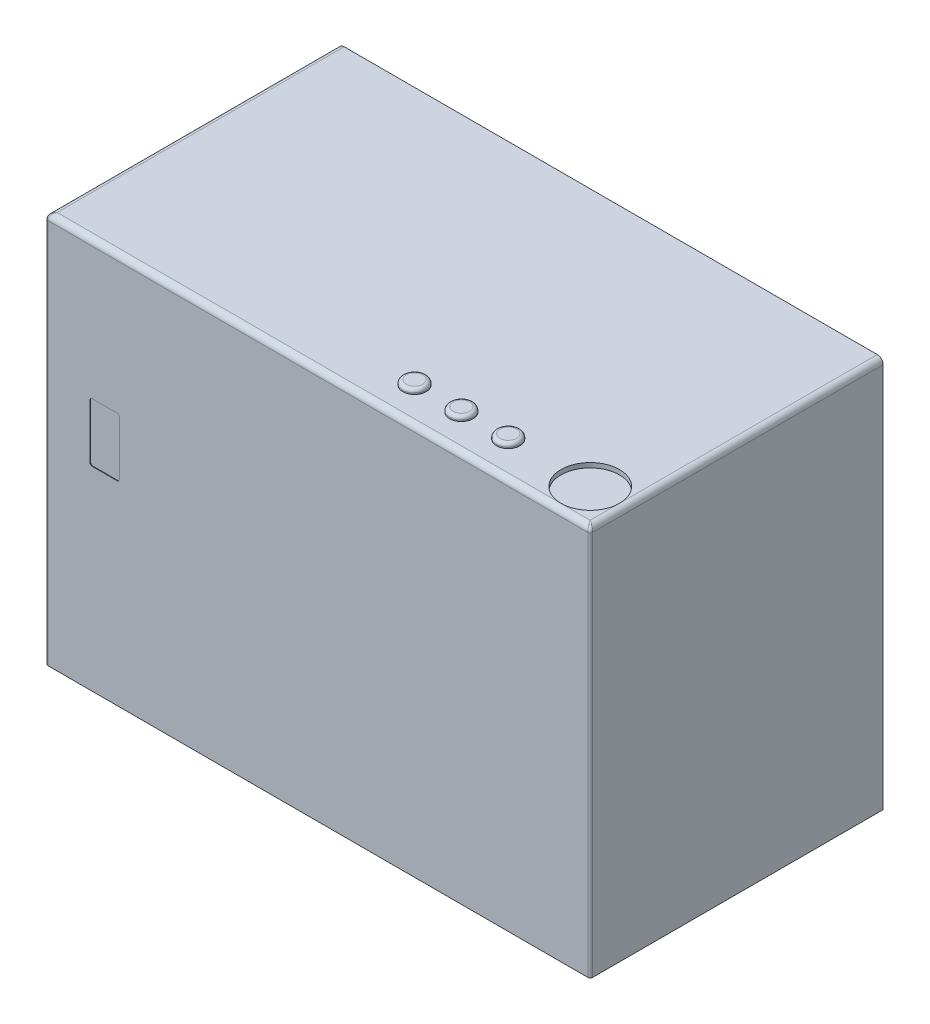
SolidWorks part; units mm, degrees
ref_plane "Front Plane" through (0, 0, 0) normal (0, 0, 1) x (1, 0, 0)
ref_plane "Top Plane" through (0, 0, 0) normal (0, 1, 0) x (1, 0, 0)
ref_plane "Right Plane" through (0, 0, 0) normal (1, 0, 0) x (0, 0, -1)
sketch "Sketch1" plane through (0, 0, 0) normal (0, 0, 1) x (1, 0, 0)
  line L1 (232.5, -167) -> (-232.5, -167)
  line L2 (232.5, -167) -> (232.5, 167)
  line L3 (232.5, 167) -> (-232.5, 167)
  line L4 (-232.5, -167) -> (-232.5, 167)
  line L5 (232.5, -167) -> (-232.5, 167) construction
  line L6 (232.5, 167) -> (-232.5, -167) construction
  point P0 (0, 0)
  dimension "D1" = 334
  dimension "D2" = 465
extrude "Boss-Extrude1" add sketch "Sketch1" along normal blind 250
sketch "Sketch2" plane through (0, -167, 0) normal (0, -1, 0) x (1, 0, 0)
  line L0 (-232.5, 250) -> (232.5, 250) construction
  line L1 (-232.5, 250) -> (-232.5, 0) construction
  line L2 (232.5, 250) -> (232.5, 0) construction
  circle A0 centre (-217.5, 230) radius 9
  circle A1 centre (217.5, 230) radius 9
  dimension "D1" = 18
  dimension "D2" = 18
  dimension "D3" = 20
  dimension "D4" = 15
  dimension "D5" = 15
  dimension "D6" = 20
extrude "Cut-Extrude1" cut sketch "Sketch2" against normal blind 10
fillet "Fillet1" radius 2 2 edges at (232.5, 0, 250) (-232.5, 0, 250)
sketch "Sketch3" plane through (0, 0, 250) normal (0, 0, 1) x (1, 0, 0)
  line L1 (-192.5382, -0.7443) -> (-171.5382, -0.7443)
  line L2 (-194.5382, 1.2557) -> (-194.5382, 47.2557)
  line L3 (-192.5382, 49.2557) -> (-171.5382, 49.2557)
  line L4 (-169.5382, 1.2557) -> (-169.5382, 47.2557)
  line L5 (-194.5382, -0.7443) -> (-169.5382, 49.2557) construction
  line L6 (-194.5382, 49.2557) -> (-169.5382, -0.7443) construction
  arc A0 (-192.5382, -0.7443) -> (-194.5382, 1.2557) centre (-192.5382, 1.2557) cw
  arc A1 (-169.5382, 1.2557) -> (-171.5382, -0.7443) centre (-171.5382, 1.2557) cw
  arc A2 (-169.5382, 47.2557) -> (-171.5382, 49.2557) centre (-171.5382, 47.2557) ccw
  arc A3 (-192.5382, 49.2557) -> (-194.5382, 47.2557) centre (-192.5382, 47.2557) ccw
  point P0 (-182.0382, 24.2557)
  dimension "D3" = 2
  dimension "D1" = 50
  dimension "D2" = 25
extrude "Cut-Extrude2" cut sketch "Sketch3" against normal blind 0.5
sketch "Sketch4" plane through (0, 167, 0) normal (0, 1, 0) x (1, 0, 0)
  line L0 (230.5, -250) -> (-230.5, -250) construction
  line L1 (232.5, -248) -> (232.5, 0) construction
  circle A0 centre (52.5, -220) radius 10
  circle A1 centre (92.5, -220) radius 10
  circle A2 centre (132.5, -220) radius 10
  dimension "D1" = 20
  dimension "D2" = 20
  dimension "D3" = 20
  dimension "D4" = 30
  dimension "D5" = 30
  dimension "D6" = 30
  dimension "D7" = 40
  dimension "D8" = 40
  dimension "D9" = 100
extrude "Boss-Extrude2" add sketch "Sketch4" along normal blind 4
fillet "Fillet2" radius 3 3 edges at (122.5, 171, 220) (82.5, 171, 220) (42.5, 171, 220)
sketch "Sketch5" plane through (0, 167, 0) normal (0, 1, 0) x (1, 0, 0)
  line L0 (230.5, -250) -> (-230.5, -250) construction
  line L1 (232.5, -248) -> (232.5, 0) construction
  circle A0 centre (202.5, -220) radius 25
  dimension "D1" = 50
  dimension "D2" = 30
  dimension "D3" = 30
extrude "Cut-Extrude3" cut sketch "Sketch5" against normal blind 4
fillet "Fillet3" radius 5 5 edges at (231.9142, 167, 249.4142) (0, 167, 250) (-231.9142, 167, 249.4142) (232.5, 167, 124) (-232.5, 167, 124)
